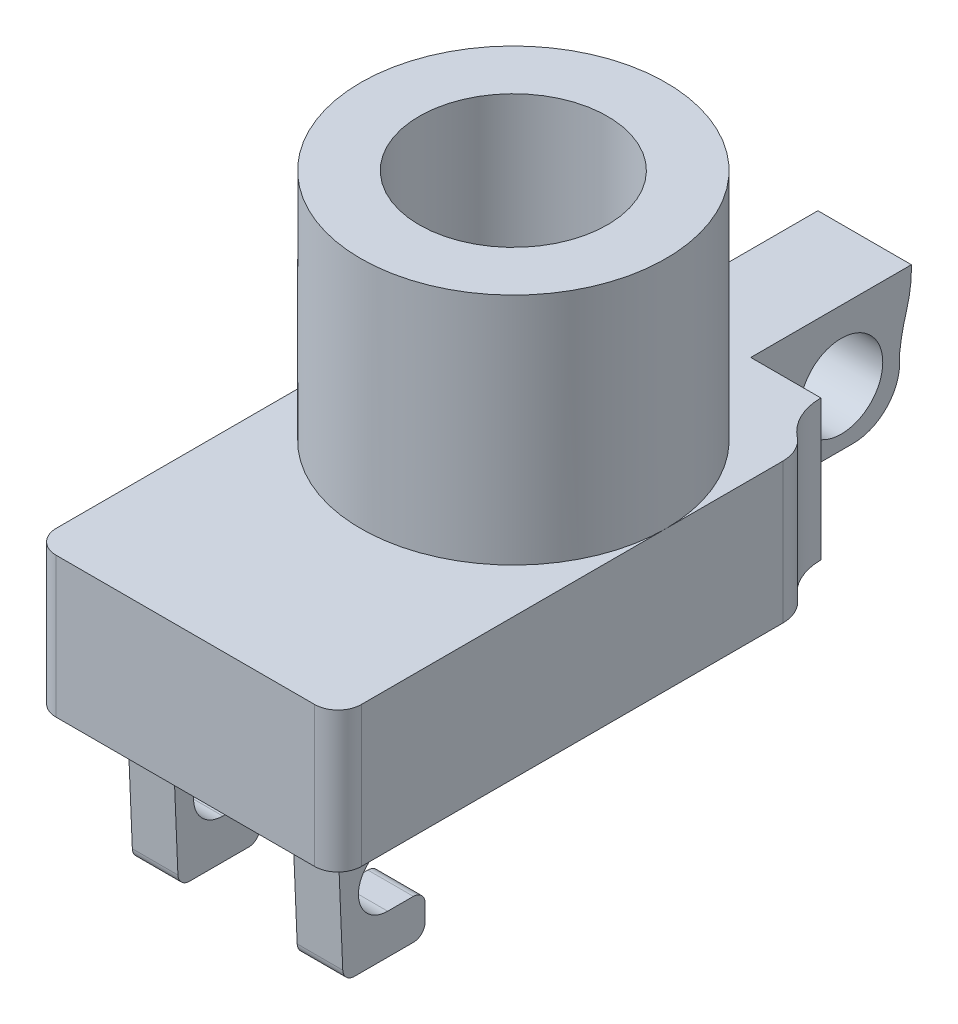
SolidWorks part; units mm, degrees
material "1060 Alloy"
ref_plane "Front Plane" through (0, 0, 0) normal (0, 0, 1) x (1, 0, 0)
ref_plane "Top Plane" through (0, 0, 0) normal (0, 1, 0) x (1, 0, 0)
ref_plane "Right Plane" through (0, 0, 0) normal (1, 0, 0) x (0, 0, -1)
sketch "Sketch1" plane through (0, 0, 0) normal (0, 1, 0) x (1, 0, 0)
  line L4 (-13.05, 8.5) -> (-13.05, -27.55)
  line L5 (-11.05, -29.55) -> (11.05, -29.55)
  line L6 (13.05, -27.55) -> (13.05, 8.5)
  line L10 (-10, 14.8089) -> (10, 14.8089)
  arc A2 (-13.05, -27.55) -> (-11.05, -29.55) centre (-11.05, -27.55) ccw
  arc A3 (11.05, -29.55) -> (13.05, -27.55) centre (11.05, -27.55) ccw
  arc A4 (13.05, 8.5) -> (11.8944, 10.8903) centre (10, 8.5) ccw
  arc A5 (10, 14.8089) -> (11.8944, 10.8903) centre (15, 14.8089) ccw
  arc A6 (-11.8944, 10.8903) -> (-10, 14.8089) centre (-15, 14.8089) ccw
  arc A7 (-11.8944, 10.8903) -> (-13.05, 8.5) centre (-10, 8.5) ccw
extrude "Boss-Extrude1" add sketch "Sketch1" along normal blind 12
sketch "Sketch2" plane through (0, 0, -14.8089) normal (0, 0, -1) x (-1, 0, 0)
  line L0 (-10, 12) -> (10, 12) construction
  line L1 (-4, 0) -> (4, 0)
  line L2 (-4, 0) -> (-4, 12)
  line L3 (-4, 12) -> (4, 12)
  line L4 (4, 0) -> (4, 12)
  line L5 (-4, 0) -> (4, 12) construction
  line L6 (-4, 12) -> (4, 0) construction
  point P0 (0, 6)
  dimension "D1" = 8
  dimension "D2" = 4
extrude "Boss-Extrude2" add sketch "Sketch2" along normal blind 14.74
sketch "Sketch3" plane through (4, 0, 0) normal (1, 0, 0) x (0, 0, -1)
  line L0 (29.5489, 12) -> (29.5489, 0) construction
  line L1 (14.8089, 0) -> (29.5489, 0)
  line L2 (14.8089, 0) -> (14.8089, 1.25)
  line L3 (14.8089, 1.25) -> (29.5489, 1.25)
  line L4 (29.5489, 0) -> (29.5489, 1.25)
  dimension "D1" = 1.25
extrude "Cut-Extrude1" cut sketch "Sketch3" against normal through all both and the other way through all
sketch "Sketch4" plane through (4, 0, 0) normal (1, 0, 0) x (0, 0, -1)
  line L0 (29.5489, 12) -> (29.5489, 1.25) construction
  line L1 (29.5489, 12) -> (14.8089, 12) construction
  circle A0 centre (22.5489, 6) radius 3.55
  dimension "D3" = 7.1
  dimension "D1" = 7
  dimension "D2" = 6
extrude "Cut-Extrude2" cut sketch "Sketch4" against normal through all both and the other way through all
sketch "Sketch6" plane through (4, 0, 0) normal (1, 0, 0) x (0, 0, -1)
  line L0 (14.8089, 1.25) -> (29.5489, 1.25) construction
  line L1 (29.5489, 12) -> (27.5489, 12)
  line L2 (29.5489, 12) -> (29.5489, 1.25)
  line L3 (29.5489, 1.25) -> (27.5489, 1.25)
  line L4 (27.5489, 12) -> (27.5489, 1.25)
  dimension "D1" = 2
extrude "Cut-Extrude3" cut sketch "Sketch6" against normal through all both and the other way through all
fillet "Fillet1" radius 4 1 edges at (0, 1.25, -27.5489)
sketch "Sketch7" plane through (4, 0, 0) normal (1, 0, 0) x (0, 0, -1)
  line L0 (27.5489, 10) -> (27.5489, 6)
  line L1 (27.5489, 12) -> (28.5489, 12)
  line L2 (27.5489, 12) -> (27.5489, 10)
  line L4 (28.5489, 12) -> (28.5489, 11.6608)
  line L5 (27.5489, 5.25) -> (27.5489, 12) construction
  arc A0 (27.5489, 6) -> (28.1222, 8.7708) centre (43.3351, 4.1785) cw
  arc A1 (28.1222, 8.7708) -> (28.5489, 11.6608) centre (18.5489, 11.6608) ccw
  point P11 (28.5489, 10)
  dimension "D4" = 10
  dimension "D1" = 1
  dimension "D2" = 2
  dimension "D3" = 4
extrude "Boss-Extrude3" add sketch "Sketch7" against normal up to surface (8 mm away) up to face at (-4, 6, -26.0989)
sketch "Sketch8" plane through (0, 12, 0) normal (0, 1, 0) x (1, 0, 0)
  line L0 (-11.05, -29.55) -> (11.05, -29.55) construction
  circle A0 centre (0, -1.5) radius 13.05
  circle A1 centre (0, -1.5) radius 8.05
  dimension "D2" = 16.1
  dimension "D1" = 28.05
extrude "Boss-Extrude4" add sketch "Sketch8" along normal blind 20
sketch "Sketch9" plane through (0, 0, 0) normal (0, -1, 0) x (1, 0, 0)
  line L0 (-11.05, 29.55) -> (11.05, 29.55) construction
  line L1 (-9, 25.55) -> (-5.1, 25.55)
  line L2 (-9, 25.55) -> (-9, 18.05)
  line L3 (-9, 18.05) -> (-5.1, 18.05)
  line L4 (-5.1, 25.55) -> (-5.1, 18.05)
  line L5 (-13.05, -8.5) -> (-13.05, 27.55) construction
  line L6 (0, 29.55) -> (0, 20.7412) construction
  line L7 (5.1, 25.55) -> (5.1, 18.05)
  line L8 (9, 18.05) -> (5.1, 18.05)
  line L9 (9, 25.55) -> (9, 18.05)
  line L10 (9, 25.55) -> (5.1, 25.55)
  dimension "D1" = 4
  dimension "D2" = 4.05
  dimension "D3" = 3.9
  dimension "D4" = 7.5
extrude "Boss-Extrude5" add sketch "Sketch9" along normal blind 11.9
sketch "Sketch10" plane through (-9, 0, 0) normal (-1, 0, 0) x (0, 0, 1)
  line L0 (25.55, -11.9) -> (18.05, -11.9) construction
  line L1 (29.55, 12) -> (29.55, 0) construction
  line L2 (21.25, -3.49) -> (13.7187, -3.49)
  line L3 (13.7187, -3.49) -> (13.7187, -8.49)
  line L4 (13.7187, -8.49) -> (21.25, -8.49)
  arc A0 (21.25, -8.49) -> (21.25, -3.49) centre (21.25, -5.99) ccw
  dimension "D3" = 5
  dimension "D1" = 5.91
  dimension "D2" = 8.3
extrude "Cut-Extrude4" cut sketch "Sketch10" against normal through all both and the other way through all
chamfer "Chamfer1" distance 11.9 distance2 0.5 2 edges at (-7.05, -11.9, 25.55) (7.05, -11.9, 25.55) first distance on face at (-7.05, -5.95, 25.55) first distance on face at (7.05, -5.95, 25.55)
fillet "Fillet3" radius 1 8 edges at (-7.05, -11.9, 25.05) (7.05, -11.9, 25.05) (7.05, -3.49, 18.05) (7.05, -8.49, 18.05) (-7.05, -3.49, 18.05) (-7.05, -8.49, 18.05) (7.05, -11.9, 18.05) (-7.05, -11.9, 18.05)
